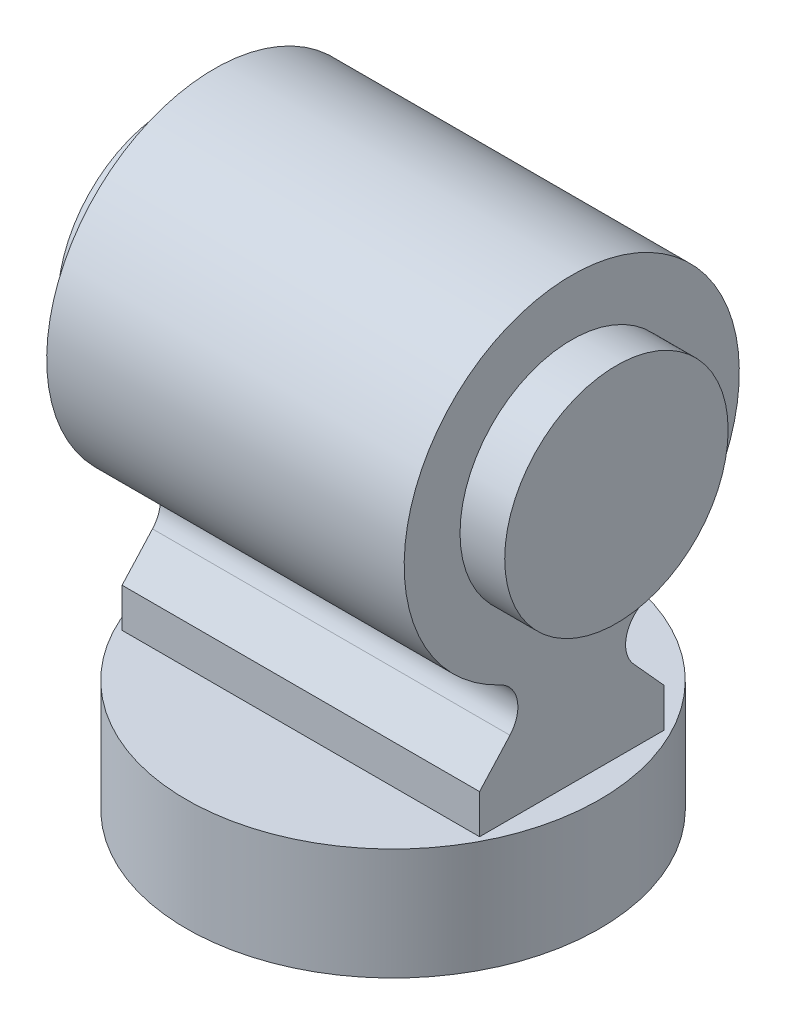
SolidWorks part; units mm, degrees
ref_plane "Front Plane" through (0, 0, 0) normal (0, 0, 1) x (1, 0, 0)
ref_plane "Top Plane" through (0, 0, 0) normal (0, 1, 0) x (1, 0, 0)
ref_plane "Right Plane" through (0, 0, 0) normal (1, 0, 0) x (0, 0, -1)
sketch "Sketch2" plane through (0, 0, 0) normal (1, 0, 0) x (0, 0, -1)
  line L0 (0, -23.7786) -> (0, -66.9385) construction
  line L1 (-11.0585, -35.8065) -> (-16.5, -41.82)
  line L2 (16.5, -41.82) -> (16.5, -48.82)
  line L3 (16.5, -48.82) -> (-16.5, -48.82)
  line L4 (11.0585, -35.8065) -> (16.5, -41.82)
  line L5 (-16.5, -41.82) -> (-16.5, -48.82)
  arc A0 (12.7992, -27.1326) -> (-12.7992, -27.1326) centre (0, 0) ccw
  arc A1 (12.7992, -27.1326) -> (11.0585, -35.8065) centre (15.15, -32.116) ccw
  arc A2 (-12.7992, -27.1326) -> (-11.0585, -35.8065) centre (-15.15, -32.116) cw
  point P18 (0, -48.82)
  dimension "D1" = 60
  dimension "D2" = 11.02
  dimension "D3" = 15.15
  dimension "D4" = 16.5
  dimension "D5" = 7
  dimension "D6" = 48.82
  dimension "D7" = 8.11
extrude "Boss-Extrude1" add sketch "Sketch2" along normal blind 32 and the other way blind 32
sketch "Sketch3" plane through (32, 0, 0) normal (1, 0, 0) x (0, 0, -1)
  circle A0 centre (0, 0) radius 20
extrude "Boss-Extrude2" add sketch "Sketch3" along normal blind 8
sketch "Sketch4" plane through (-32, 0, 0) normal (-1, 0, 0) x (0, 0, 1)
  circle A0 centre (0, 0) radius 20
extrude "Boss-Extrude3" add sketch "Sketch4" along normal blind 8
sketch "Sketch5" plane through (0, -48.82, 0) normal (0, -1, 0) x (1, 0, 0)
  circle A0 centre (0, 0) radius 37
  dimension "D1" = 74
extrude "Boss-Extrude4" add sketch "Sketch5" along normal blind 20
